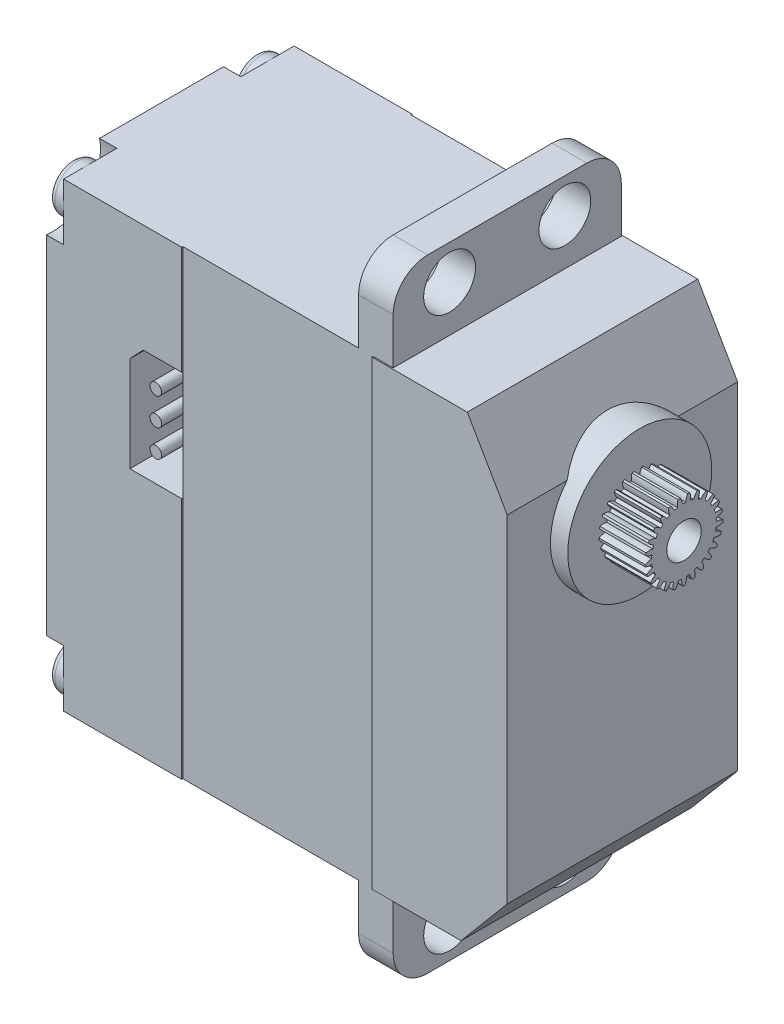
SolidWorks part; units mm, degrees
ref_plane "前视基准面" through (0, 0, 0) normal (0, 0, 1) x (1, 0, 0)
ref_plane "上视基准面" through (0, 0, 0) normal (0, 1, 0) x (1, 0, 0)
ref_plane "右视基准面" through (0, 0, 0) normal (1, 0, 0) x (0, 0, -1)
sketch "草图1" plane through (0, 0, 0) normal (0, 0, 1) x (1, 0, 0)
  line L1 (-20, -20) -> (20, -20)
  line L2 (-20, -20) -> (-20, 20)
  line L3 (-20, 20) -> (20, 20)
  line L4 (20, -20) -> (20, 20)
  line L5 (-20, -20) -> (20, 20) construction
  line L6 (-20, 20) -> (20, -20) construction
  point P0 (0, 0)
  dimension "D1" = 40
  dimension "D2" = 40
extrude "凸台-拉伸1" add sketch "草图1" along normal blind 20
ref_plane "基准面1" through (20, 0, 0) normal (1, 0, 0) x (0, 0, -1)
sketch "草图2" plane through (20, 0, 0) normal (1, 0, 0) x (0, 0, -1)
  line L0 (-10, 20) -> (-10, 10) construction
  line L1 (-20, 20) -> (0, 20) construction
  circle A0 centre (-10, 10) radius 6.25
  dimension "D2" = 12.5
  dimension "D1" = 10
extrude "凸台-拉伸2" add sketch "草图2" along normal blind 1.5
ref_plane "基准面2" through (-20, 0, 0) normal (-1, 0, 0) x (0, 0, 1)
ref_plane "基准面5" through (20, 0, 0) normal (1, 0, 0) x (0, 0, -1)
ref_plane "基准面8" through (0, 0, 0) normal (0, 0, -1) x (-1, 0, 0)
sketch "草图10" plane through (0, 0, 0) normal (0, 0, -1) x (-1, 0, 0)
  line L0 (-20, 20) -> (20, 20) construction
  line L1 (-8.25, -20) -> (8.25, -20)
  line L2 (-8.25, -20) -> (-8.25, 20)
  line L3 (-8.25, 20) -> (8.25, 20)
  line L4 (8.25, -20) -> (8.25, 20)
  line L5 (-8.25, -20) -> (8.25, 20) construction
  line L6 (-8.25, 20) -> (8.25, -20) construction
  point P0 (0, 0)
  dimension "D1" = 16.5
extrude "切除-拉伸5" cut sketch "草图10" against normal blind 0.1
ref_plane "基准面9" through (0, 0, 20) normal (0, 0, 1) x (1, 0, 0)
sketch "草图11" plane through (0, 0, 20) normal (0, 0, 1) x (1, 0, 0)
  line L0 (20, 20) -> (-20, 20) construction
  line L1 (-8.25, -20) -> (8.25, -20)
  line L2 (-8.25, -20) -> (-8.25, 20)
  line L3 (-8.25, 20) -> (8.25, 20)
  line L4 (8.25, -20) -> (8.25, 20)
  line L5 (-8.25, -20) -> (8.25, 20) construction
  line L6 (-8.25, 20) -> (8.25, -20) construction
  point P0 (0, 0)
  dimension "D1" = 16.5
extrude "切除-拉伸6" cut sketch "草图11" against normal blind 0.1
ref_plane "基准面10" through (0, 20, 0) normal (0, 1, 0) x (1, 0, 0)
ref_plane "基准面11" through (0, -20, 0) normal (0, -1, 0) x (-1, 0, 0)
ref_plane "基准面12" through (21.5, 0, 0) normal (1, 0, 0) x (0, 0, -1)
sketch "草图14" plane through (21.5, 0, 0) normal (1, 0, 0) x (0, 0, -1)
  arc A0 (-9.0018, 13.0728) -> (-9.3214, 12.5861) centre (-8.1454, 12.1623) ccw
  arc A1 (-9.3214, 12.5861) -> (-9.5931, 12.6558) centre (-10.1556, 9.9012) ccw
  arc A2 (-9.5931, 12.6558) -> (-9.6387, 13.2363) centre (-10.8278, 12.851) ccw
  arc A3 (-9.6387, 13.2363) -> (-9.8268, 13.2601) centre (-10.1556, 9.9012) ccw
  arc A4 (-9.8268, 13.2601) -> (-10.0153, 12.7092) centre (-8.7709, 12.5912) ccw
  arc A5 (-10.0153, 12.7092) -> (-10.2958, 12.7092) centre (-10.1556, 9.9012) ccw
  arc A6 (-10.2958, 12.7092) -> (-10.4843, 13.2601) centre (-11.5402, 12.5912) ccw
  arc A7 (-10.4843, 13.2601) -> (-10.6725, 13.2363) centre (-10.1556, 9.9012) ccw
  arc A8 (-10.6725, 13.2363) -> (-10.718, 12.6558) centre (-9.4834, 12.851) ccw
  arc A9 (-10.718, 12.6558) -> (-10.9897, 12.5861) centre (-10.1556, 9.9012) ccw
  arc A10 (-10.9897, 12.5861) -> (-11.3093, 13.0728) centre (-12.1657, 12.1623) ccw
  arc A11 (-11.3093, 13.0728) -> (-11.4857, 13.003) centre (-10.1556, 9.9012) ccw
  arc A12 (-11.4857, 13.003) -> (-11.3854, 12.4294) centre (-10.2381, 12.9255) ccw
  arc A13 (-11.3854, 12.4294) -> (-11.6312, 12.2943) centre (-10.1556, 9.9012) ccw
  arc A14 (-11.6312, 12.2943) -> (-12.0618, 12.6863) centre (-12.6649, 11.5913) ccw
  arc A15 (-12.0618, 12.6863) -> (-12.2153, 12.5748) centre (-10.1556, 9.9012) ccw
  arc A16 (-12.2153, 12.5748) -> (-11.9755, 12.0441) centre (-10.9876, 12.81) ccw
  arc A17 (-11.9755, 12.0441) -> (-12.18, 11.8521) centre (-10.1556, 9.9012) ccw
  arc A18 (-12.18, 11.8521) -> (-12.6946, 12.1247) centre (-13.0064, 10.9142) ccw
  arc A19 (-12.6946, 12.1247) -> (-12.8155, 11.9785) centre (-10.1556, 9.9012) ccw
  arc A20 (-12.8155, 11.9785) -> (-12.4513, 11.5242) centre (-11.6848, 12.5117) ccw
  arc A21 (-12.4513, 11.5242) -> (-12.6016, 11.2873) centre (-10.1556, 9.9012) ccw
  arc A22 (-12.6016, 11.2873) -> (-13.1678, 11.4234) centre (-13.1688, 10.1734) ccw
  arc A23 (-13.1678, 11.4234) -> (-13.2485, 11.2518) centre (-10.1556, 9.9012) ccw
  arc A24 (-13.2485, 11.2518) -> (-12.7828, 10.9023) centre (-12.286, 12.0493) ccw
  arc A25 (-12.7828, 10.9023) -> (-12.8695, 10.6355) centre (-10.1556, 9.9012) ccw
  arc A26 (-12.8695, 10.6355) -> (-13.4517, 10.6265) centre (-13.1418, 9.4155) ccw
  arc A27 (-13.4517, 10.6265) -> (-13.4872, 10.4402) centre (-10.1556, 9.9012) ccw
  arc A28 (-13.4872, 10.4402) -> (-12.9492, 10.2175) centre (-12.7533, 11.452) ccw
  arc A29 (-12.9492, 10.2175) -> (-12.9668, 9.9375) centre (-10.1556, 9.9012) ccw
  arc A30 (-12.9668, 9.9375) -> (-13.5285, 9.784) centre (-12.9272, 8.6881) ccw
  arc A31 (-13.5285, 9.784) -> (-13.5166, 9.5947) centre (-10.1556, 9.9012) ccw
  arc A32 (-13.5166, 9.5947) -> (-12.9401, 9.5128) centre (-13.0574, 10.7573) ccw
  arc A33 (-12.9401, 9.5128) -> (-12.8875, 9.2372) centre (-10.1556, 9.9012) ccw
  arc A34 (-12.8875, 9.2372) -> (-13.3934, 8.9488) centre (-12.5384, 8.0369) ccw
  arc A35 (-13.3934, 8.9488) -> (-13.3348, 8.7685) centre (-10.1556, 9.9012) ccw
  arc A36 (-13.3348, 8.7685) -> (-12.756, 8.8325) centre (-13.1791, 10.0087) ccw
  arc A37 (-12.756, 8.8325) -> (-12.6366, 8.5787) centre (-10.1556, 9.9012) ccw
  arc A38 (-12.6366, 8.5787) -> (-13.0549, 8.1735) centre (-12, 7.5029) ccw
  arc A39 (-13.0549, 8.1735) -> (-12.9532, 8.0134) centre (-10.1556, 9.9012) ccw
  arc A40 (-12.9532, 8.0134) -> (-12.4086, 8.2194) centre (-13.1109, 9.2534) ccw
  arc A41 (-12.4086, 8.2194) -> (-12.2298, 8.0032) centre (-10.1556, 9.9012) ccw
  arc A42 (-12.2298, 8.0032) -> (-12.5341, 7.5068) centre (-11.3456, 7.1196) ccw
  arc A43 (-12.5341, 7.5068) -> (-12.3959, 7.3769) centre (-10.1556, 9.9012) ccw
  arc A44 (-12.3959, 7.3769) -> (-11.9195, 7.7119) centre (-12.8569, 8.5388) ccw
  arc A45 (-11.9195, 7.7119) -> (-11.6926, 7.547) centre (-10.1556, 9.9012) ccw
  arc A46 (-11.6926, 7.547) -> (-11.8639, 6.9905) centre (-10.6165, 6.911) ccw
  arc A47 (-11.8639, 6.9905) -> (-11.6977, 6.8991) centre (-10.1556, 9.9012) ccw
  arc A48 (-11.6977, 6.8991) -> (-11.3197, 7.342) centre (-12.4333, 7.9098) ccw
  arc A49 (-11.3197, 7.342) -> (-11.0588, 7.2387) centre (-10.1556, 9.9012) ccw
  arc A50 (-11.0588, 7.2387) -> (-11.0864, 6.6571) centre (-9.8584, 6.8903) ccw
  arc A51 (-11.0864, 6.6571) -> (-10.9027, 6.6099) centre (-10.1556, 9.9012) ccw
  arc A52 (-10.9027, 6.6099) -> (-10.6467, 7.1329) centre (-11.8665, 7.4059) ccw
  arc A53 (-10.6467, 7.1329) -> (-10.3683, 7.0977) centre (-10.1556, 9.9012) ccw
  arc A54 (-10.3683, 7.0977) -> (-10.2504, 6.5275) centre (-9.1189, 7.0588) ccw
  arc A55 (-10.2504, 6.5275) -> (-10.0607, 6.5275) centre (-10.1556, 9.9012) ccw
  arc A56 (-10.0607, 6.5275) -> (-9.9428, 7.0977) centre (-11.1922, 7.0588) ccw
  arc A57 (-9.9428, 7.0977) -> (-9.6645, 7.1329) centre (-10.1556, 9.9012) ccw
  arc A58 (-9.6645, 7.1329) -> (-9.4084, 6.6099) centre (-8.4447, 7.4059) ccw
  arc A59 (-9.4084, 6.6099) -> (-9.2247, 6.6571) centre (-10.1556, 9.9012) ccw
  arc A60 (-9.2247, 6.6571) -> (-9.2523, 7.2387) centre (-10.4528, 6.8903) ccw
  arc A61 (-9.2523, 7.2387) -> (-8.9915, 7.342) centre (-10.1556, 9.9012) ccw
  arc A62 (-8.9915, 7.342) -> (-8.6134, 6.8991) centre (-7.8779, 7.9098) ccw
  arc A63 (-8.6134, 6.8991) -> (-8.4472, 6.9905) centre (-10.1556, 9.9012) ccw
  arc A64 (-8.4472, 6.9905) -> (-8.6185, 7.547) centre (-9.6947, 6.911) ccw
  arc A65 (-8.6185, 7.547) -> (-8.3916, 7.7119) centre (-10.1556, 9.9012) ccw
  arc A66 (-8.3916, 7.7119) -> (-7.9153, 7.3769) centre (-7.4542, 8.5388) ccw
  arc A67 (-7.9153, 7.3769) -> (-7.777, 7.5068) centre (-10.1556, 9.9012) ccw
  arc A68 (-7.777, 7.5068) -> (-8.0814, 8.0032) centre (-8.9655, 7.1196) ccw
  arc A69 (-8.0814, 8.0032) -> (-7.9026, 8.2194) centre (-10.1556, 9.9012) ccw
  arc A70 (-7.9026, 8.2194) -> (-7.3579, 8.0134) centre (-7.2003, 9.2534) ccw
  arc A71 (-7.3579, 8.0134) -> (-7.2563, 8.1735) centre (-10.1556, 9.9012) ccw
  arc A72 (-7.2563, 8.1735) -> (-7.6745, 8.5787) centre (-8.3112, 7.5029) ccw
  arc A73 (-7.6745, 8.5787) -> (-7.5551, 8.8325) centre (-10.1556, 9.9012) ccw
  arc A74 (-7.5551, 8.8325) -> (-6.9763, 8.7685) centre (-7.132, 10.0087) ccw
  arc A75 (-6.9763, 8.7685) -> (-6.9177, 8.9488) centre (-10.1556, 9.9012) ccw
  arc A76 (-6.9177, 8.9488) -> (-7.4236, 9.2372) centre (-7.7727, 8.0369) ccw
  arc A77 (-7.4236, 9.2372) -> (-7.371, 9.5128) centre (-10.1556, 9.9012) ccw
  arc A78 (-7.371, 9.5128) -> (-6.7945, 9.5947) centre (-7.2538, 10.7573) ccw
  arc A79 (-6.7945, 9.5947) -> (-6.7826, 9.784) centre (-10.1556, 9.9012) ccw
  arc A80 (-6.7826, 9.784) -> (-7.3443, 9.9375) centre (-7.3839, 8.6881) ccw
  arc A81 (-7.3443, 9.9375) -> (-7.3619, 10.2175) centre (-10.1556, 9.9012) ccw
  arc A82 (-7.3619, 10.2175) -> (-6.8239, 10.4402) centre (-7.5578, 11.452) ccw
  arc A83 (-6.8239, 10.4402) -> (-6.8594, 10.6265) centre (-10.1556, 9.9012) ccw
  arc A84 (-6.8594, 10.6265) -> (-7.4417, 10.6355) centre (-7.1693, 9.4155) ccw
  arc A85 (-7.4417, 10.6355) -> (-7.5283, 10.9023) centre (-10.1556, 9.9012) ccw
  arc A86 (-7.5283, 10.9023) -> (-7.0626, 11.2518) centre (-8.0251, 12.0493) ccw
  arc A87 (-7.0626, 11.2518) -> (-7.1434, 11.4234) centre (-10.1556, 9.9012) ccw
  arc A88 (-7.1434, 11.4234) -> (-7.7095, 11.2873) centre (-7.1424, 10.1734) ccw
  arc A89 (-7.7095, 11.2873) -> (-7.8599, 11.5242) centre (-10.1556, 9.9012) ccw
  arc A90 (-7.8599, 11.5242) -> (-7.4957, 11.9785) centre (-8.6263, 12.5117) ccw
  arc A91 (-7.4957, 11.9785) -> (-7.6166, 12.1247) centre (-10.1556, 9.9012) ccw
  arc A92 (-7.6166, 12.1247) -> (-8.1311, 11.8521) centre (-7.3047, 10.9142) ccw
  arc A93 (-8.1311, 11.8521) -> (-8.3356, 12.0441) centre (-10.1556, 9.9012) ccw
  arc A94 (-8.3356, 12.0441) -> (-8.0959, 12.5748) centre (-9.3235, 12.81) ccw
  arc A95 (-8.0959, 12.5748) -> (-8.2493, 12.6863) centre (-10.1556, 9.9012) ccw
  arc A96 (-8.2493, 12.6863) -> (-8.6799, 12.2943) centre (-7.6462, 11.5913) ccw
  arc A97 (-8.6799, 12.2943) -> (-8.9257, 12.4294) centre (-10.1556, 9.9012) ccw
  arc A98 (-8.9257, 12.4294) -> (-8.8255, 13.003) centre (-10.0731, 12.9255) ccw
  arc A99 (-8.8255, 13.003) -> (-9.0018, 13.0728) centre (-10.1556, 9.9012) ccw
extrude "凸台-拉伸6" add sketch "草图14" along normal blind 4
ref_plane "基准面13" through (25.5, 0, 0) normal (1, 0, 0) x (0, 0, -1)
sketch "草图15" plane through (25.5, 0, 0) normal (1, 0, 0) x (0, 0, -1)
  circle A0 centre (-10.1556, 9.9012) radius 1.5
extrude "切除-拉伸9" cut sketch "草图15" against normal blind 4
ref_plane "基准面14" through (0, 20, 0) normal (0, 1, 0) x (1, 0, 0)
ref_plane "基准面15" through (-20, 0, 0) normal (-1, 0, 0) x (0, 0, 1)
chamfer "倒角2" distance 6 angle 30 1 edges at (20, 20, 10) first distance on face at (20, 0, 10)
chamfer "倒角3" distance 4 angle 50 1 edges at (20, -20, 10) first distance on face at (0, -20, 10)
ref_plane "基准面18" through (0, -20, 0) normal (0, -1, 0) x (-1, 0, 0)
sketch "草图20" plane through (0, -20, 0) normal (0, -1, 0) x (-1, 0, 0)
  line L0 (-20, 1.0461) -> (-20, -15.8444) construction
  line L2 (-20, 0) -> (-7, 0) construction
  line L3 (6.4625, 0) -> (-6.4625, 0) construction
  line L4 (-7, 0) -> (-7, -0.8546) construction
  line L7 (-5.9416, -19.9) -> (-4.5261, -19.9) construction
  line L9 (-6.0182, -0.1) -> (-4.3371, -0.1) construction
  line L10 (-7, -0.1) -> (-7, -19.9) construction
  line L11 (-7, -19.9) -> (-10, -19.9) construction
  line L12 (-10, -19.9) -> (-10, 0) construction
  line L13 (-10, 0) -> (-7, 0) construction
  line L14 (-10, -0.1) -> (-7, -0.1)
  line L15 (-7, -0.1) -> (-7, -19.9)
  line L16 (-7, -19.9) -> (-10, -19.9)
  line L17 (-10, -19.9) -> (-10, -0.1)
extrude "凸台-拉伸8" add sketch "草图20" along normal blind 7
sketch "草图21" plane through (0, 20, 0) normal (0, 1, 0) x (1, 0, 0)
  line L6 (7, -19.9) -> (10, -19.9)
  line L7 (7, -0.1) -> (7, -19.9)
  line L8 (10, -0.1) -> (7, -0.1)
  line L9 (10, -19.9) -> (10, -0.1)
  line L10 (7, -19.9) -> (10, -19.9)
  line L11 (7, -0.1) -> (7, -19.9)
  line L12 (10, -0.1) -> (7, -0.1)
  line L13 (10, -19.9) -> (10, -0.1)
  dimension "D1" = 0
extrude "凸台-拉伸9" add sketch "草图21" along normal blind 7
fillet "圆角4" radius 3 4 edges at (8.5, 27, 19.9) (8.5, 27, 0.1) (8.5, -27, 19.9) (8.5, -27, 0.1)
ref_plane "基准面19" through (10, 0, 0) normal (1, 0, 0) x (0, 0, -1)
sketch "草图22" plane through (10, 0, 0) normal (1, 0, 0) x (0, 0, -1)
  line L3 (-20.5235, 0) -> (-0.5503, 0) construction
  circle A0 centre (-15, 24) radius 2.25
  circle A1 centre (-5, 24) radius 2.25
  circle A2 centre (-5, -24) radius 2.25
  circle A3 centre (-15, -24) radius 2.25
extrude "切除-拉伸12" cut sketch "草图22" against normal blind 7.3
sketch "草图24" plane through (-20, 0, 0) normal (-1, 0, 0) x (0, 0, 1)
  line L0 (20, 0) -> (0, 0) construction
  line L1 (20, -6.4625) -> (20, 6.4625) construction
  line L2 (10, 0) -> (10, 28.881) construction
  line L3 (0, 6.4625) -> (0, -6.4625) construction
  line L4 (11, 20) -> (-11, 20) construction
  line L5 (0, 15.0598) -> (0, 20)
  line L6 (0, 20) -> (4.6197, 20)
  line L7 (20, 15.0598) -> (20, 20)
  line L8 (20, 20) -> (15.3803, 20)
  line L9 (0, -20) -> (4.6197, -20)
  line L10 (0, -15.0598) -> (0, -20)
  line L11 (20, -20) -> (15.3803, -20)
  line L12 (20, -15.0598) -> (20, -20)
  arc A1 (4.6197, 20) -> (0, 15.0598) centre (0.55, 19.1756) cw
  arc A2 (15.3803, 20) -> (20, 15.0598) centre (19.45, 19.1756) ccw
  arc A3 (4.6197, -20) -> (0, -15.0598) centre (0.55, -19.1756) ccw
  arc A5 (15.3803, -20) -> (20, -15.0598) centre (19.45, -19.1756) cw
extrude "切除-拉伸13" cut sketch "草图24" against normal blind 1.5
ref_plane "基准面20" through (-18.5, 0, 0) normal (-1, 0, 0) x (0, 0, 1)
sketch "草图25" plane through (-18.5, 0, 0) normal (-1, 0, 0) x (0, 0, 1)
  line L0 (0, 0) -> (20, 0) construction
  line L1 (20, -6.4625) -> (20, 6.4625) construction
  line L2 (10, 0) -> (10, 8.1993) construction
  circle A0 centre (2.0399, 17.9472) radius 2
  circle A1 centre (17.9601, 17.9472) radius 2
  circle A2 centre (2.0399, -17.9472) radius 2
  circle A3 centre (17.9601, -17.9472) radius 2
extrude "凸台-拉伸10" add sketch "草图25" along normal blind 1.3
fillet "圆角5" radius 0.5 4 edges at (-19.8, -17.9472, 19.9601) (-19.8, -17.9472, 0.0399) (-19.8, 17.9472, 15.9601) (-19.8, 17.9472, 4.0399)
ref_plane "基准面21" through (-19.8, 0, 0) normal (-1, 0, 0) x (0, 0, 1)
sketch "草图26" plane through (-19.8, 0, 0) normal (-1, 0, 0) x (0, 0, 1)
  line L0 (1.6399, 18.3472) -> (0.5942, 18.3472)
  line L1 (1.6399, 16.5015) -> (2.4399, 16.5015)
  line L2 (1.6399, 16.5015) -> (1.6399, 17.5472)
  line L3 (1.6399, 19.3929) -> (2.4399, 19.3929)
  line L4 (2.4399, 16.5015) -> (2.4399, 17.5472)
  line L5 (1.6399, 16.5015) -> (2.4399, 19.3929) construction
  line L6 (1.6399, 19.3929) -> (2.4399, 16.5015) construction
  line L7 (3.4855, 17.5472) -> (2.4399, 17.5472)
  line L8 (3.4855, 17.5472) -> (3.4855, 18.3472)
  line L9 (3.4855, 18.3472) -> (2.4399, 18.3472)
  line L10 (0.5942, 17.5472) -> (0.5942, 18.3472)
  line L11 (3.4855, 17.5472) -> (0.5942, 18.3472) construction
  line L12 (3.4855, 18.3472) -> (0.5942, 17.5472) construction
  line L13 (2.4399, 18.3472) -> (2.4399, 19.3929)
  line L14 (1.6399, 17.5472) -> (0.5942, 17.5472)
  line L15 (1.6399, 18.3472) -> (1.6399, 19.3929)
  line L16 (0, 0) -> (20.0276, 0) construction
  line L17 (10.0138, 0) -> (10.0138, 3.4562) construction
  line L18 (16.542, 18.3472) -> (19.4334, 17.5472) construction
  line L19 (16.542, 17.5472) -> (19.4334, 18.3472) construction
  line L20 (18.3877, 19.3929) -> (17.5877, 16.5015) construction
  line L21 (18.3877, 16.5015) -> (17.5877, 19.3929) construction
  line L22 (18.3877, 18.3472) -> (18.3877, 19.3929)
  line L23 (18.3877, 17.5472) -> (19.4334, 17.5472)
  line L24 (17.5877, 18.3472) -> (17.5877, 19.3929)
  line L25 (19.4334, 17.5472) -> (19.4334, 18.3472)
  line L26 (16.542, 18.3472) -> (17.5877, 18.3472)
  line L27 (16.542, 17.5472) -> (16.542, 18.3472)
  line L28 (16.542, 17.5472) -> (17.5877, 17.5472)
  line L29 (17.5877, 16.5015) -> (17.5877, 17.5472)
  line L30 (18.3877, 19.3929) -> (17.5877, 19.3929)
  line L31 (18.3877, 16.5015) -> (18.3877, 17.5472)
  line L32 (18.3877, 16.5015) -> (17.5877, 16.5015)
  line L33 (18.3877, 18.3472) -> (19.4334, 18.3472)
  line L34 (18.3877, -16.5015) -> (17.5877, -19.3929) construction
  line L35 (18.3877, -19.3929) -> (17.5877, -16.5015) construction
  line L36 (16.542, -17.5472) -> (19.4334, -18.3472) construction
  line L37 (16.542, -18.3472) -> (19.4334, -17.5472) construction
  line L38 (3.4855, -18.3472) -> (0.5942, -17.5472) construction
  line L39 (3.4855, -17.5472) -> (0.5942, -18.3472) construction
  line L40 (1.6399, -19.3929) -> (2.4399, -16.5015) construction
  line L41 (1.6399, -16.5015) -> (2.4399, -19.3929) construction
  line L42 (18.3877, -18.3472) -> (19.4334, -18.3472)
  line L43 (18.3877, -16.5015) -> (17.5877, -16.5015)
  line L44 (18.3877, -16.5015) -> (18.3877, -17.5472)
  line L45 (18.3877, -19.3929) -> (17.5877, -19.3929)
  line L46 (17.5877, -16.5015) -> (17.5877, -17.5472)
  line L47 (16.542, -17.5472) -> (17.5877, -17.5472)
  line L48 (16.542, -17.5472) -> (16.542, -18.3472)
  line L49 (16.542, -18.3472) -> (17.5877, -18.3472)
  line L50 (19.4334, -17.5472) -> (19.4334, -18.3472)
  line L51 (17.5877, -18.3472) -> (17.5877, -19.3929)
  line L52 (18.3877, -17.5472) -> (19.4334, -17.5472)
  line L53 (18.3877, -18.3472) -> (18.3877, -19.3929)
  line L54 (1.6399, -18.3472) -> (1.6399, -19.3929)
  line L55 (1.6399, -17.5472) -> (0.5942, -17.5472)
  line L56 (2.4399, -18.3472) -> (2.4399, -19.3929)
  line L57 (0.5942, -17.5472) -> (0.5942, -18.3472)
  line L58 (3.4855, -18.3472) -> (2.4399, -18.3472)
  line L59 (3.4855, -17.5472) -> (3.4855, -18.3472)
  line L60 (3.4855, -17.5472) -> (2.4399, -17.5472)
  line L61 (2.4399, -16.5015) -> (2.4399, -17.5472)
  line L62 (1.6399, -19.3929) -> (2.4399, -19.3929)
  line L63 (1.6399, -16.5015) -> (1.6399, -17.5472)
  line L64 (1.6399, -16.5015) -> (2.4399, -16.5015)
  line L65 (1.6399, -18.3472) -> (0.5942, -18.3472)
  circle A0 centre (2.0399, 17.9472) radius 1.5 construction
  point P0 (2.0399, 17.9472)
  point P8 (2.0399, 17.9472)
  point P34 (17.9877, 17.9472)
  point P59 (17.9877, -17.9472)
  point P60 (2.0399, -17.9472)
extrude "切除-拉伸14" cut sketch "草图26" against normal blind 0.8 draft 16
ref_plane "基准面22" through (0, 20, 0) normal (0, 1, 0) x (1, 0, 0)
ref_plane "基准面23" through (0, 0, -1.9) normal (0, 0, -1) x (-1, 0, 0)
sketch "草图27" plane through (0, 0, -1.9) normal (0, 0, -1) x (-1, 0, 0)
  line L0 (11.5965, 10.6) -> (8.25, 10.6) construction
  line L1 (12.75, 9.3676) -> (11.5965, 10.6) construction
  line L2 (12.75, 1.1) -> (12.75, 9.3676) construction
  line L3 (8.25, 1.1) -> (8.25, 10.6) construction
  line L4 (8.25, 1.1) -> (12.75, 1.1) construction
  line L5 (11.5965, 10.6) -> (8.25, 10.6)
  line L6 (12.75, 9.3676) -> (11.5965, 10.6)
  line L7 (12.75, 1.1) -> (12.75, 9.3676)
  line L8 (8.25, 1.1) -> (8.25, 10.6)
  line L9 (8.25, 1.1) -> (12.75, 1.1)
extrude "切除-拉伸15" cut sketch "草图27" against normal blind 7
ref_plane "基准面24" through (0, 0, 22) normal (0, 0, 1) x (1, 0, 0)
sketch "草图28" plane through (0, 0, 22) normal (0, 0, 1) x (1, 0, 0)
  line L5 (-11.5965, 10.6) -> (-12.75, 9.3676)
  line L6 (-8.25, 10.6) -> (-11.5965, 10.6)
  line L7 (-8.25, 1.1) -> (-8.25, 10.6)
  line L8 (-12.75, 1.1) -> (-8.25, 1.1)
  line L9 (-12.75, 9.3676) -> (-12.75, 1.1)
  line L10 (-11.5965, 10.6) -> (-12.75, 9.3676)
  line L11 (-8.25, 10.6) -> (-11.5965, 10.6)
  line L12 (-8.25, 1.1) -> (-8.25, 10.6)
  line L13 (-12.75, 1.1) -> (-8.25, 1.1)
  line L14 (-12.75, 9.3676) -> (-12.75, 1.1)
  dimension "D1" = 0
extrude "切除-拉伸16" cut sketch "草图28" against normal blind 7
sketch "草图30" plane through (0, 0, 5.1) normal (0, 0, -1) x (-1, 0, 0)
  circle A0 centre (10.5, 8.225) radius 0.5 construction
  circle A1 centre (10.5, 3.475) radius 0.5 construction
  circle A2 centre (10.5, 5.85) radius 0.5 construction
  circle A3 centre (10.5, 8.225) radius 0.5
  circle A4 centre (10.5, 3.475) radius 0.5
  circle A5 centre (10.5, 5.85) radius 0.5
extrude "凸台-拉伸11" add sketch "草图30" along normal blind 5
sketch "草图31" plane through (0, 0, 15) normal (0, 0, 1) x (1, 0, 0)
  circle A0 centre (-10.5, 5.85) radius 0.5 construction
  circle A1 centre (-10.5, 3.475) radius 0.5 construction
  circle A2 centre (-10.5, 5.85) radius 0.5
  circle A3 centre (-10.5, 3.475) radius 0.5
  circle A5 centre (-10.5, 8.225) radius 0.5
  circle A6 centre (-10.5, 8.225) radius 0.5
  dimension "D1" = 0
extrude "凸台-拉伸12" add sketch "草图31" along normal blind 5
